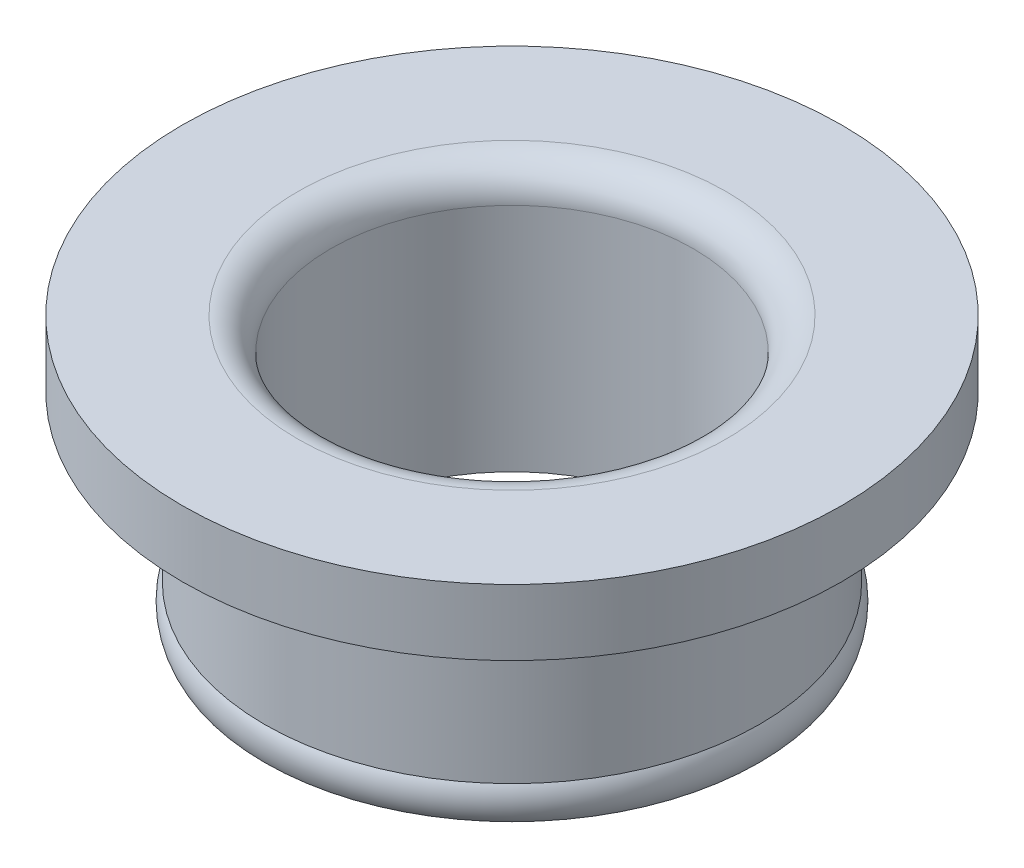
SolidWorks part; units mm, degrees
ref_plane "Front Plane" through (0, 0, 0) normal (0, 0, 1) x (1, 0, 0)
ref_plane "Top Plane" through (0, 0, 0) normal (0, 1, 0) x (1, 0, 0)
ref_plane "Right Plane" through (0, 0, 0) normal (1, 0, 0) x (0, 0, -1)
sketch "Sketch1" plane through (0, 0, 0) normal (0, 1, 0) x (1, 0, 0)
  circle A0 centre (0, 0) radius 6.985
  circle A1 centre (0, 0) radius 12.7
  circle A2 centre (0, 0) radius 9.525
  dimension "D1" = 13.97
  dimension "D2" = 25.4
  dimension "D3" = 19.05
extrude "Boss-Extrude1" add sketch "Sketch1" along normal blind 2.54 contours A0 | A1 region at (0, 0, 0)
extrude "Boss-Extrude2" add sketch "Sketch1<3>" against normal blind 7.62 contours A2 A0 region at (-9.2556, 0, 0)
sketch "Sketch1<3>" plane through (0, 0, 0) normal (0, 1, 0) x (1, 0, 0) same geometry as "Sketch1"
fillet "Fillet1" radius 1.27 1 edges at (0, 2.54, 6.985)
fillet "Fillet2" radius 0.762 1 edges at (0, 0, 9.525)
sketch "Sketch2" plane through (0, 0, 0) normal (1, 0, 0) x (0, 0, -1)
  line L0 (9.525, -7.62) -> (9.525, -0.762) construction
  line L1 (9.525, -6.35) -> (9.525, -7.62)
  arc A0 (9.525, -7.62) -> (9.525, -6.35) centre (8.4251, -6.985) ccw
  dimension "D1" = 1.27
  dimension "D2" = 1.27
ref_axis "Axis1" through (0, 3.048, 0) along (0, -1, 0)
revolve "Revolve1" add sketch "Sketch2" angle 360 about axis through (0, 3.048, 0) along (0, -1, 0)
